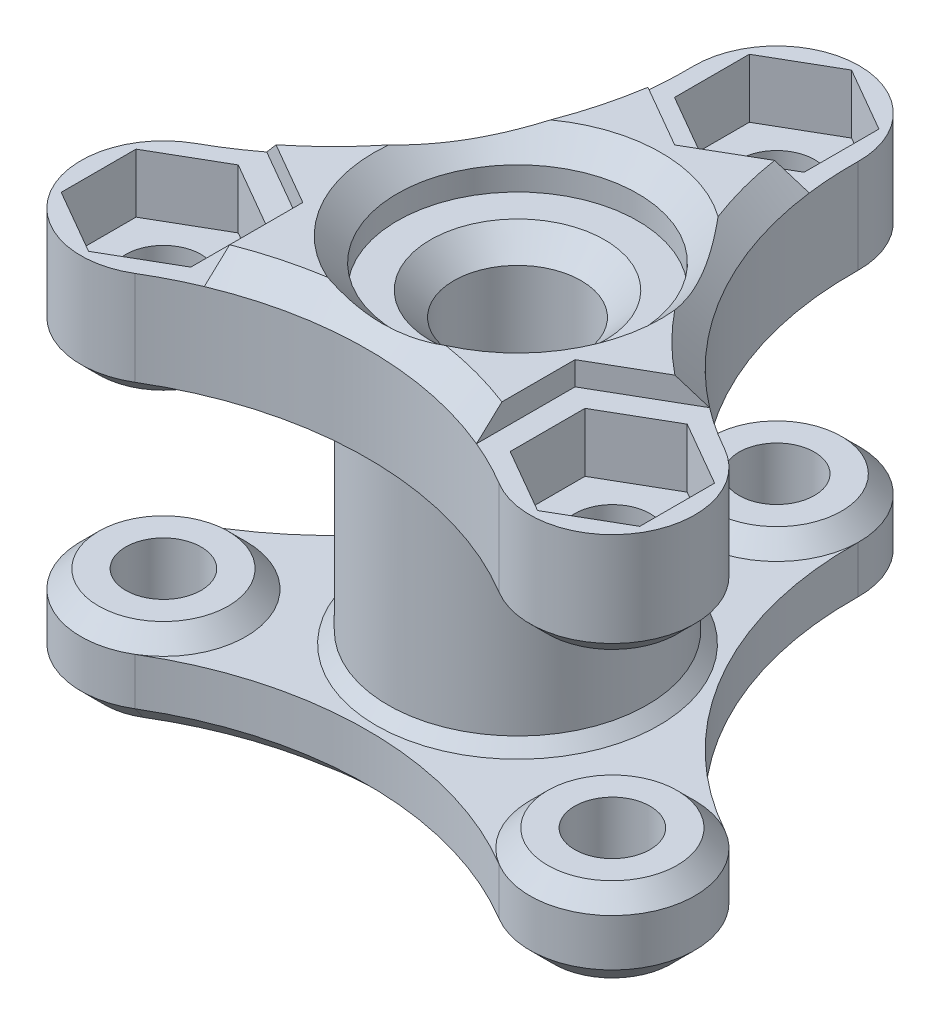
SolidWorks part; units mm, degrees
ref_plane "Front Plane" through (0, 0, 0) normal (0, 0, 1) x (1, 0, 0)
ref_plane "Top Plane" through (0, 0, 0) normal (0, 1, 0) x (1, 0, 0)
ref_plane "Right Plane" through (0, 0, 0) normal (1, 0, 0) x (0, 0, -1)
sketch "Sketch1" plane through (0, 0, 0) normal (0, 1, 0) x (1, 0, 0)
  line L0 (-14.5, 14.5) -> (14.5, 14.5) construction
  line L5 (-9.5263, -5.5) -> (9.5263, -5.5) construction
  line L6 (-14.5, 0) -> (-14.5, 14.5) construction
  line L7 (14.5, 0) -> (14.5, 14.5) construction
  line L8 (-14.5, 12.6) -> (14.5, 12.6) construction
  line L9 (0, 11) -> (-9.5263, -5.5) construction
  line L11 (0, 11) -> (9.5263, -5.5) construction
  circle A0 centre (0, 0) radius 14.5 construction
  circle A3 centre (0, 11) radius 1.6
  circle A5 centre (9.5263, -5.5) radius 1.6
  circle A6 centre (-9.5263, -5.5) radius 1.6
  circle A8 centre (0, 11) radius 5 construction
  arc A12 (3.4995, 10.9393) -> (-3.4995, 10.9393) centre (0, 11) ccw
  arc A15 (7.724, -8.5003) -> (-7.724, -8.5003) centre (0, -21.3588) ccw
  arc A21 (7.724, -8.5003) -> (11.2235, -2.439) centre (9.5263, -5.5) ccw
  arc A24 (-11.2235, -2.439) -> (-7.724, -8.5003) centre (-9.5263, -5.5) ccw
  circle A25 centre (0, 0) radius 17.2765 construction
  circle A27 centre (0, 0) radius 2.7
  circle A28 centre (0, 0) radius 11 construction
  arc A30 (-3.4995, 10.9393) -> (-11.2235, -2.439) centre (-18.4972, 10.6794) cw
  arc A31 (3.4995, 10.9393) -> (11.2235, -2.439) centre (18.4972, 10.6794) ccw
  point P3 (-3.5725, 11.423)
  point P6 (-3.5, 11)
  point P43 (0, 0)
  dimension "D1" = 29
  dimension "D2" = 5.4
  dimension "D3" = 3.2
  dimension "D4" = 10
  dimension "D5" = 22
  dimension "D6" = 15
extrude "Boss-Extrude1" add sketch "Sketch1" along normal blind 3
sketch "Sketch2" plane through (0, 3, 0) normal (0, 1, 0) x (1, 0, 0)
  circle A0 centre (0, 0) radius 5.5
  circle A2 centre (0, 11) radius 5 construction
  circle A7 centre (0, 0) radius 2.7 construction
  circle A8 centre (0, 0) radius 2.7
  dimension "D1" = 11
  dimension "D3" = 10
extrude "Boss-Extrude2" add sketch "Sketch2" along normal blind 10
sketch "Sketch3" plane through (0, 13, 0) normal (0, 1, 0) x (1, 0, 0)
  circle A1 centre (-9.5263, -5.5) radius 1.6 construction
  circle A6 centre (0, 0) radius 2.7 construction
  circle A8 centre (0, 0) radius 2.7
  circle A14 centre (9.5263, -5.5) radius 1.6 construction
  circle A17 centre (0, 11) radius 1.6 construction
  circle A18 centre (-9.5263, -5.5) radius 1.6
  circle A19 centre (9.5263, -5.5) radius 1.6
  circle A22 centre (0, 11) radius 1.6
  arc A23 (3.4995, 10.9393) -> (-3.4995, 10.9393) centre (0, 11) ccw
  arc A24 (-11.2235, -2.439) -> (-3.4995, 10.9393) centre (-18.4972, 10.6794) ccw
  arc A25 (-11.2235, -2.439) -> (-3.4995, 10.9393) centre (-18.4972, 10.6794) ccw
  arc A26 (3.4995, 10.9393) -> (11.2235, -2.439) centre (18.4972, 10.6794) ccw
  arc A27 (-11.2235, -2.439) -> (-7.724, -8.5003) centre (-9.5263, -5.5) ccw
  arc A28 (7.724, -8.5003) -> (-7.724, -8.5003) centre (0, -21.3588) ccw
  arc A29 (7.724, -8.5003) -> (11.2235, -2.439) centre (9.5263, -5.5) ccw
  arc A30 (3.4995, 10.9393) -> (11.2235, -2.439) centre (18.4972, 10.6794) ccw
  arc A33 (3.4995, 10.9393) -> (-3.4995, 10.9393) centre (0, 11) ccw
  arc A37 (-11.2235, -2.439) -> (-7.724, -8.5003) centre (-9.5263, -5.5) ccw
  arc A38 (7.724, -8.5003) -> (-7.724, -8.5003) centre (0, -21.3588) ccw
  arc A39 (7.724, -8.5003) -> (11.2235, -2.439) centre (9.5263, -5.5) ccw
  dimension "D1" = 0
extrude "Boss-Extrude3" add sketch "Sketch3" along normal blind 5
sketch "Sketch6" plane through (0, 18, 0) normal (0, -1, 0) x (1, 0, 0)
  line L0 (-12.2763, 3.9123) -> (-9.5263, 2.3246)
  line L17 (2.75, -12.5877) -> (2.75, -9.4123)
  line L18 (2.75, -9.4123) -> (0, -7.8246)
  line L19 (0, -7.8246) -> (-2.75, -9.4123)
  line L20 (-2.75, -9.4123) -> (-2.75, -12.5877)
  line L21 (-2.75, -12.5877) -> (0, -14.1754)
  line L22 (0, -14.1754) -> (2.75, -12.5877)
  line L23 (-9.5263, 2.3246) -> (-6.7763, 3.9123)
  line L24 (-6.7763, 3.9123) -> (-6.7763, 7.0877)
  line L25 (-6.7763, 7.0877) -> (-9.5263, 8.6754)
  line L26 (-9.5263, 8.6754) -> (-12.2763, 7.0877)
  line L27 (-12.2763, 7.0877) -> (-12.2763, 3.9123)
  line L28 (9.5263, 8.6754) -> (6.7763, 7.0877)
  line L29 (6.7763, 7.0877) -> (6.7763, 3.9123)
  line L30 (6.7763, 3.9123) -> (9.5263, 2.3246)
  line L31 (9.5263, 2.3246) -> (12.2763, 3.9123)
  line L32 (12.2763, 3.9123) -> (12.2763, 7.0877)
  line L33 (12.2763, 7.0877) -> (9.5263, 8.6754)
  circle A0 centre (0, -11) radius 2.75 construction
  circle A2 centre (-9.5263, 5.5) radius 2.75 construction
  circle A3 centre (9.5263, 5.5) radius 2.75 construction
  point P1 (-10.4616, -3.3992)
  point P8 (0, 0)
  point P10 (-9.5263, 5.5)
  point P45 (0, 0)
  dimension "D1" = 5.5
  dimension "D2" = 3
extrude "Cut-Extrude2" cut sketch "Sketch6" along normal blind 3.5
sketch "Sketch8" plane through (0, 3, 0) normal (0, 1, 0) x (1, 0, 0)
  circle A0 centre (-9.5263, -5.5) radius 2.5
  circle A1 centre (-9.5263, -5.5) radius 1.6 construction
  circle A2 centre (-9.5263, -5.5) radius 1.6
  circle A3 centre (0, 11) radius 2.5
  circle A4 centre (0, 11) radius 1.6
  circle A5 centre (9.5263, -5.5) radius 2.5
  circle A6 centre (9.5263, -5.5) radius 1.6
  circle A12 centre (9.5263, -5.5) radius 1.6 construction
  point P0 (9.6564, -5.2289)
  point P2 (-12.9661, 20.8758)
  point P6 (-9.5263, -5.6616)
  point P24 (0, 0)
  dimension "D1" = 5
  dimension "D2" = 3
extrude "Boss-Extrude5" add sketch "Sketch8" along normal blind 0.75
sketch "Sketch9" plane through (0, 13, 0) normal (0, -1, 0) x (1, 0, 0)
  circle A0 centre (0, -11) radius 2.5
  circle A1 centre (0, -11) radius 1.6 construction
  circle A2 centre (0, -11) radius 1.6
  circle A3 centre (-9.5263, 5.5) radius 2.5
  circle A4 centre (-9.5263, 5.5) radius 1.6
  circle A5 centre (9.5263, 5.5) radius 2.5
  circle A6 centre (9.5263, 5.5) radius 1.6
  point P6 (0, 0)
  point P7 (-9.5263, 5.5)
  point P25 (0, 0)
  dimension "D1" = 5
  dimension "D2" = 3
extrude "Boss-Extrude6" add sketch "Sketch9" along normal blind 0.75
sketch "Sketch10" plane through (0, 18, 0) normal (0, 1, 0) x (1, 0, 0)
  circle A0 centre (0, 0) radius 5.1
  dimension "D1" = 10.2
extrude "Cut-Extrude3" cut sketch "Sketch10" against normal blind 2
sketch "Sketch11" plane through (0, 0, 0) normal (0, -1, 0) x (1, 0, 0)
  circle A0 centre (0, 0) radius 5.1
  dimension "D1" = 10.2
extrude "Cut-Extrude4" cut sketch "Sketch11" against normal blind 3
chamfer "Chamfer1" distance 1 angle 45 12 edges at (0, 0, -14.5) (12.5574, 0, 7.25) (0, 0, 6.3588) (-12.5574, 0, 7.25) (0, 18, -14.5) (-12.5574, 18, 7.25) (12.5574, 18, 7.25) (0, 18, 6.3588) (5.5068, 0, -3.1794) (-5.5068, 0, -3.1794) (-5.5068, 18, -3.1794) (5.5068, 18, -3.1794)
chamfer "Chamfer2" distance 1 angle 45 2 edges at (0, 0, -5.1) (0, 18, 5.1)
chamfer "Chamfer3" distance 1 angle 45 6 edges at (9.5263, 3, 3) (0, 3, -13.5) (-9.5263, 3, 3) (9.5263, 13, 8) (0, 13, -8.5) (-9.5263, 13, 8)
sketch "Sketch12" plane through (0, 18, 0) normal (0, 1, 0) x (1, 0, 0)
  line L61 (3.75, 13.1651) -> (0, 15.3301)
  line L62 (0, 15.3301) -> (-3.75, 13.1651)
  line L63 (-3.75, 13.1651) -> (-3.75, 8.8349)
  line L64 (-3.75, 8.8349) -> (0, 6.6699)
  line L65 (0, 6.6699) -> (3.75, 8.8349)
  line L66 (3.75, 8.8349) -> (3.75, 13.1651)
  line L67 (2.75, 12.5877) -> (0, 14.1754)
  line L68 (0, 14.1754) -> (-2.75, 12.5877)
  line L69 (-2.75, 12.5877) -> (-2.75, 9.4123)
  line L70 (-2.75, 9.4123) -> (0, 7.8246)
  line L71 (0, 7.8246) -> (2.75, 9.4123)
  line L72 (2.75, 9.4123) -> (2.75, 12.5877)
  line L73 (2.75, 12.5877) -> (0, 14.1754)
  line L74 (0, 14.1754) -> (-2.75, 12.5877)
  line L75 (-2.75, 12.5877) -> (-2.75, 9.4123)
  line L76 (-2.75, 9.4123) -> (0, 7.8246)
  line L77 (0, 7.8246) -> (2.75, 9.4123)
  line L78 (2.75, 9.4123) -> (2.75, 12.5877)
  line L79 (9.5263, -9.8301) -> (13.2763, -7.6651)
  line L80 (13.2763, -7.6651) -> (13.2763, -3.3349)
  line L81 (13.2763, -3.3349) -> (9.5263, -1.1699)
  line L82 (9.5263, -1.1699) -> (5.7763, -3.3349)
  line L83 (5.7763, -3.3349) -> (5.7763, -7.6651)
  line L84 (5.7763, -7.6651) -> (9.5263, -9.8301)
  line L85 (9.5263, -8.6754) -> (12.2763, -7.0877)
  line L86 (12.2763, -7.0877) -> (12.2763, -3.9123)
  line L87 (12.2763, -3.9123) -> (9.5263, -2.3246)
  line L88 (9.5263, -2.3246) -> (6.7763, -3.9123)
  line L89 (6.7763, -3.9123) -> (6.7763, -7.0877)
  line L90 (6.7763, -7.0877) -> (9.5263, -8.6754)
  line L91 (-13.2763, -3.3349) -> (-13.2763, -7.6651)
  line L92 (-13.2763, -7.6651) -> (-9.5263, -9.8301)
  line L93 (-9.5263, -9.8301) -> (-5.7763, -7.6651)
  line L94 (-5.7763, -7.6651) -> (-5.7763, -3.3349)
  line L95 (-5.7763, -3.3349) -> (-9.5263, -1.1699)
  line L96 (-9.5263, -1.1699) -> (-13.2763, -3.3349)
  line L97 (-12.2763, -3.9123) -> (-12.2763, -7.0877)
  line L98 (-12.2763, -7.0877) -> (-9.5263, -8.6754)
  line L99 (-9.5263, -8.6754) -> (-6.7763, -7.0877)
  line L100 (-6.7763, -7.0877) -> (-6.7763, -3.9123)
  line L101 (-6.7763, -3.9123) -> (-9.5263, -2.3246)
  line L102 (-9.5263, -2.3246) -> (-12.2763, -3.9123)
  point P14 (0, 0)
  point P44 (0, 0)
  dimension "D1" = 0
  dimension "D2" = 1
  dimension "D3" = 3
extrude "Cut-Extrude5" cut sketch "Sketch12" against normal blind 1
chamfer "Chamfer4" distance 0.5 angle 45 2 edges at (0, 13, 5.5) (0, 3, 5.5)
chamfer "Chamfer5" distance 1 angle 45 2 edges at (0, 16, 2.7) (0, 3, -2.7)
